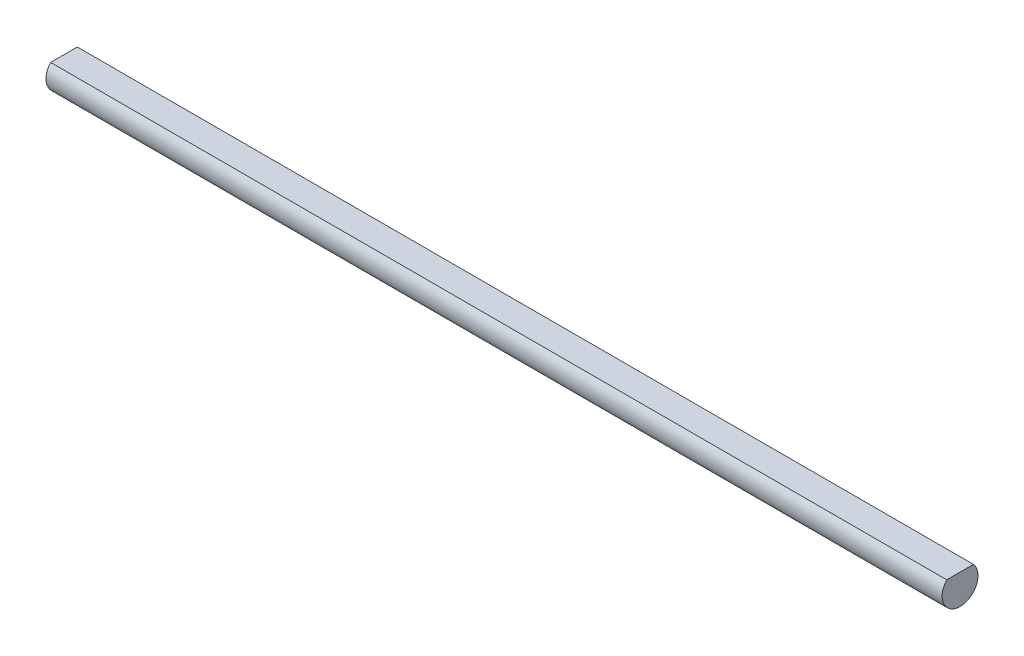
SolidWorks part; units mm, degrees
ref_plane "Front Plane" through (0, 0, 0) normal (0, 0, 1) x (1, 0, 0)
ref_plane "Top Plane" through (0, 0, 0) normal (0, 1, 0) x (1, 0, 0)
ref_plane "Right Plane" through (0, 0, 0) normal (1, 0, 0) x (0, 0, -1)
sketch "Sketch1" plane through (0, 0, 0) normal (1, 0, 0) x (0, 0, -1)
  line L0 (-2.2361, 2) -> (2.2361, 2)
  arc A0 (-2.2361, 2) -> (2.2361, 2) centre (0, 0) ccw
  dimension "D1" = 6
  dimension "D2" = 2
extrude "Boss-Extrude1" add sketch "Sketch1" along normal mid plane 150
